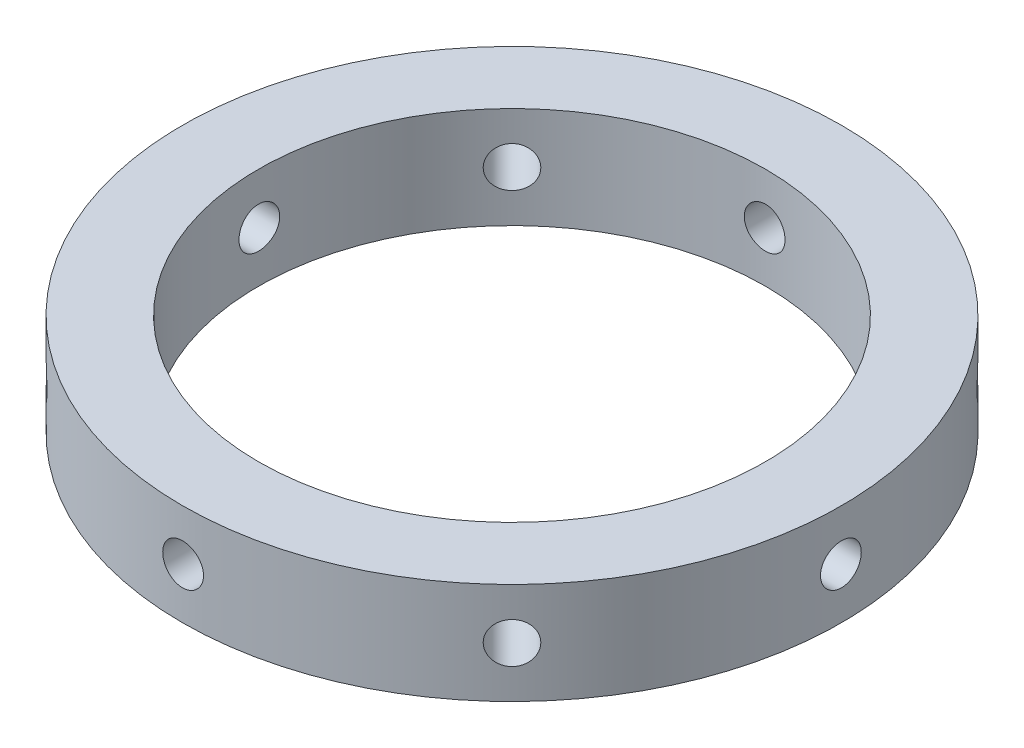
SolidWorks part; units mm, degrees
material "6061-T6 (SS)"
ref_plane "Front Plane" through (0, 0, 0) normal (0, 0, 1) x (1, 0, 0)
ref_plane "Top Plane" through (0, 0, 0) normal (0, 1, 0) x (1, 0, 0)
ref_plane "Right Plane" through (0, 0, 0) normal (1, 0, 0) x (0, 0, -1)
sketch "Sketch1" plane through (0, 0, 0) normal (0, 1, 0) x (1, 0, 0)
  circle A0 centre (0, 0) radius 31.75
  circle A1 centre (0, 0) radius 41.275
  dimension "D1" = 63.5
  dimension "D2" = 82.55
extrude "Boss-Extrude1" add sketch "Sketch1" along normal blind 12.7
ref_axis "Axis1" through (0, -0.3175, 0) along (0, 1, 0)
ref_plane "Plane1" through (0, 6.35, 0) normal (0, 1, 0) x (1, 0, 0)
ref_axis "Axis2" through (0, 6.35, -88.99) along (0, 0, 1)
hole_wizard "#7 (0.201) Diameter Hole1" positions "3DSketch2" profile "Sketch3" hole size "#7" standard "ANSI Inch"
sketch3d "3DSketch2"
  line L0 (0, 6.35, -88.99) -> (0, 6.35, 88.99) construction
  point P0 (0, 6.35, 41.275)
sketch "Sketch3" plane through (0, 6.35, 41.275) normal (1, 0, 0) x (0, -1, 0)
  line L0 (0, 0) -> (0, 13.2178)
  line L1 (0, 13.2178) -> (2.5527, 11.684)
  line L2 (2.5527, 11.684) -> (2.5527, 0)
  line L5 (2.5527, 0) -> (0, 0)
  line L10 (0, 13.2178) -> (-2.5527, 11.684) construction
  line L11 (0, -6.35) -> (0, 107.95) construction
  dimension "Hole Dia." = 5.1054
  dimension "Hole Depth" = 11.684
  dimension "Drill Angle" = 118
cosmetic thread "Cosmetic Thread2" parameters "D1"=6.604, "D2"=6.35
pattern_circular "CirPattern1" count 8 over 360 about axis through (0, -0.3175, 0) along (0, 1, 0) of "#7 (0.201) Diameter Hole1"
